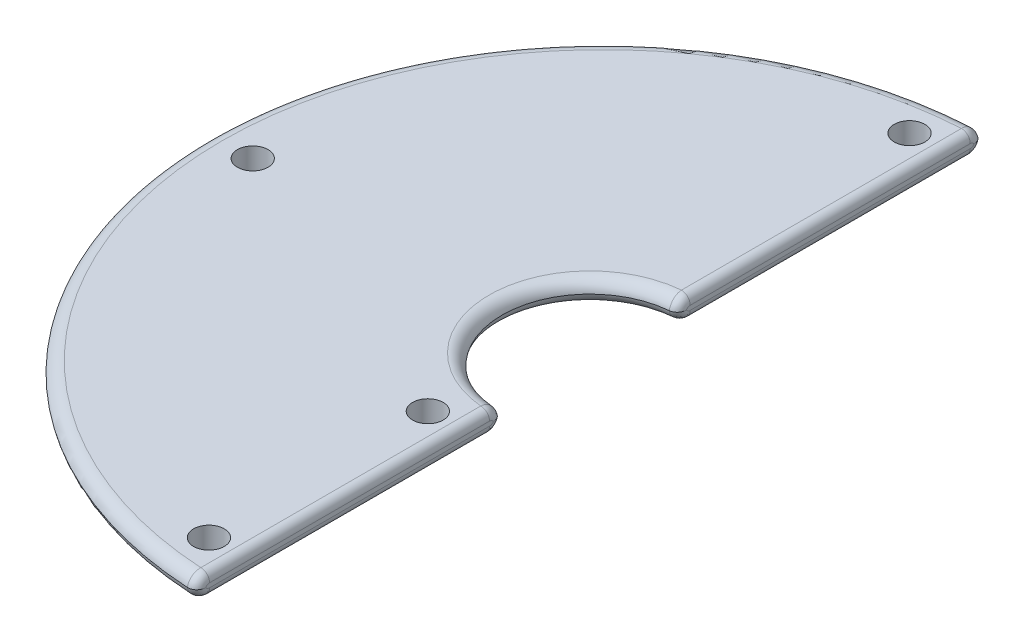
SolidWorks part; units mm, degrees
ref_plane "Front Plane" through (0, 0, 0) normal (0, 0, 1) x (1, 0, 0)
ref_plane "Top Plane" through (0, 0, 0) normal (0, 1, 0) x (1, 0, 0)
ref_plane "Right Plane" through (0, 0, 0) normal (1, 0, 0) x (0, 0, -1)
sketch "Sketch1" plane through (0, 0, 0) normal (0, 1, 0) x (1, 0, 0)
  line L1 (0, 45) -> (90, 45)
  line L2 (0, 45) -> (0, -90)
  line L3 (0, -90) -> (90, -90)
  line L4 (90, 45) -> (90, -90)
  circle A0 centre (0, 0) radius 45
extrude "Boss-Extrude1" add sketch "Sketch1" along normal blind 2.5 contours L2 A0 region at (-19.0986, 0, 0)
sketch "Sketch2" plane through (0, 2.5, 0) normal (0, 1, 0) x (1, 0, 0)
  circle A0 centre (-5, 40) radius 1.75
  circle A1 centre (-5, -40) radius 1.75
  circle A2 centre (-40, 0) radius 1.75
  circle A3 centre (-5, -15) radius 1.75
sketch "Sketch3" plane through (0, 2.5, 0) normal (0, 1, 0) x (1, 0, 0)
  line L1 (0, 45) -> (-1.5, 45)
  line L2 (0, 45) -> (0, -90)
  line L3 (0, -90) -> (-1.5, -90)
  line L4 (-1.5, 45) -> (-1.5, -90)
extrude "Cut-Extrude3" cut sketch "Sketch3" against normal blind 5
sketch "Sketch4" plane through (0, 2.5, 0) normal (0, 1, 0) x (1, 0, 0)
  line L0 (-1.5, 44.975) -> (-1.5, -44.975) construction
  circle A0 centre (-1.5, 0) radius 10
extrude "Cut-Extrude4" cut sketch "Sketch4" against normal blind 5
extrude "Cut-Extrude5" cut sketch "Sketch2" against normal blind 5
fillet "Fillet3" radius 1.5 2 edges at (-45, 0, 0) (-45, 2.5, 0)
fillet "Fillet6" radius 1.5 2 edges at (-11.5, 0, 0) (-11.5, 2.5, 0)
fillet "Fillet11" radius 1 6 edges at (-1.5, 0.3544, -10.5318) (-1.5, 2.1456, -10.5318) (-1.5, 0, -27.4871) (-1.5, 0.329, -44.4121) (-1.5, 1.9366, -44.6464) (-1.5, 2.5, -27.4871)
fillet "Fillet12" radius 1 6 edges at (-1.5, 2.171, 44.4121) (-1.5, 0.5634, 44.6464) (-1.5, 0, 27.4871) (-1.5, 0.3544, 10.5318) (-1.5, 2.1456, 10.5318) (-1.5, 2.5, 27.4871)
